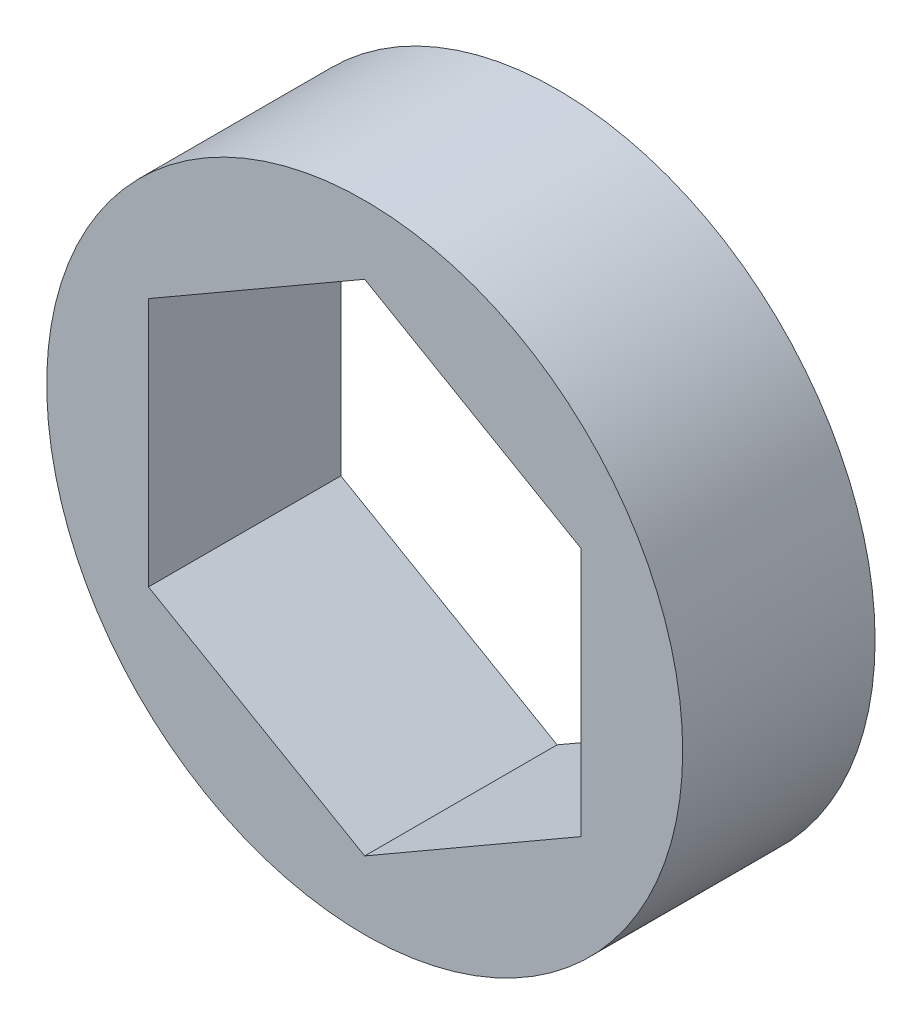
SolidWorks part; units mm, degrees
material "PET"
ref_plane "Front Plane" through (0, 0, 0) normal (0, 0, 1) x (1, 0, 0)
ref_plane "Top Plane" through (0, 0, 0) normal (0, 1, 0) x (1, 0, 0)
ref_plane "Right Plane" through (0, 0, 0) normal (1, 0, 0) x (0, 0, -1)
sketch "Sketch1" plane through (0, 0, 0) normal (0, 0, 1) x (1, 0, 0)
  line L1 (0, 7.479) -> (-6.477, 3.7395)
  line L2 (-6.477, 3.7395) -> (-6.477, -3.7395)
  line L3 (-6.477, -3.7395) -> (0, -7.479)
  line L4 (0, -7.479) -> (6.477, -3.7395)
  line L5 (6.477, -3.7395) -> (6.477, 3.7395)
  line L6 (6.477, 3.7395) -> (0, 7.479)
  circle A0 centre (0, 0) radius 6.477 construction
  circle A1 centre (0, 0) radius 9.525
  dimension "D1" = 12.954
  dimension "D2" = 19.05
extrude "Boss-Extrude1" add sketch "Sketch1" along normal mid plane 5.7633
